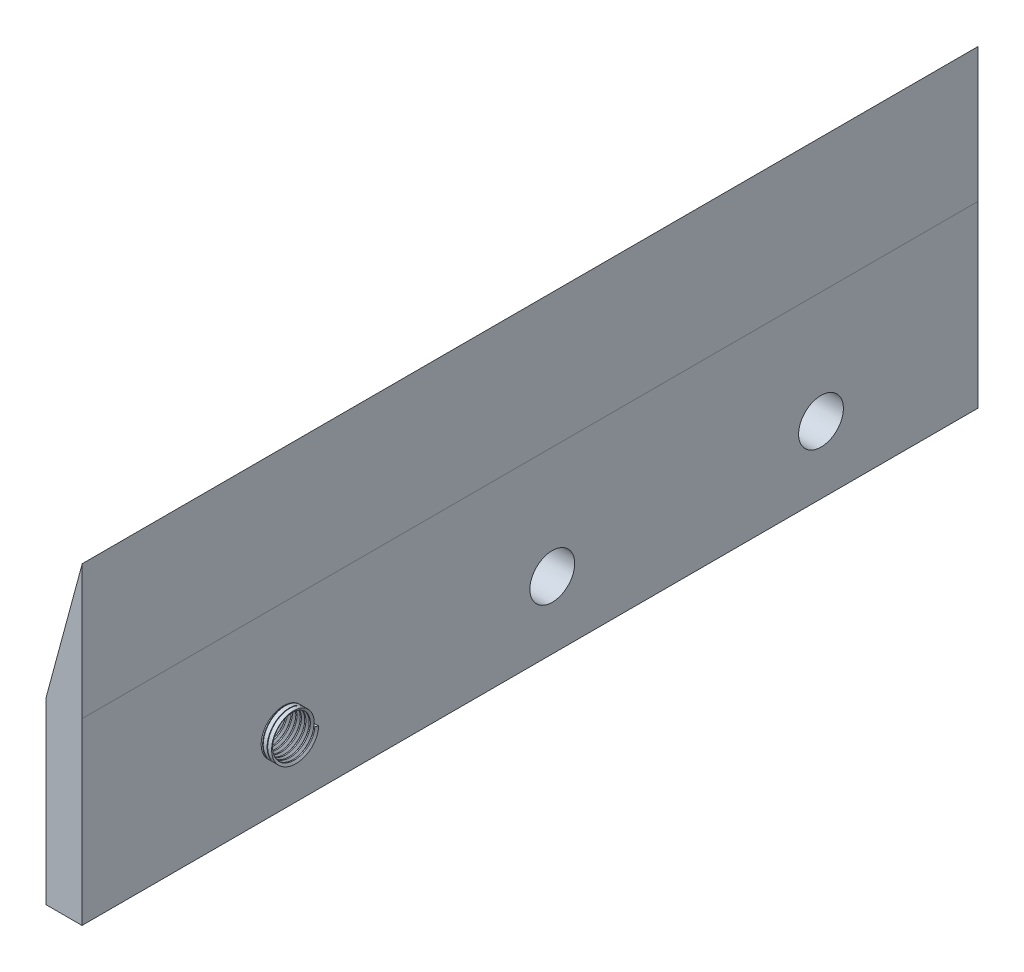
SolidWorks part; units mm, degrees
ref_plane "前基準面" through (0, 0, 0) normal (0, 0, 1) x (1, 0, 0)
ref_plane "上基準面" through (0, 0, 0) normal (0, 1, 0) x (1, 0, 0)
ref_plane "右基準面" through (0, 0, 0) normal (1, 0, 0) x (0, 0, -1)
sketch "草圖1" plane through (0, 0, 0) normal (0, 0, 1) x (1, 0, 0)
  line L0 (206.6624, 1001.1769) -> (198.624, 1001.1769)
  line L1 (198.624, 1001.1769) -> (198.624, 1041.1769)
  line L4 (206.7148, 1071.1628) -> (198.624, 1041.1769) construction
  line L5 (206.7148, 1071.1628) -> (198.624, 1041.1769)
  line L6 (206.7148, 1071.1628) -> (206.6624, 1041.1629) construction
  line L7 (206.7148, 1071.1628) -> (206.6624, 1041.1629)
  line L8 (206.6624, 1041.1629) -> (206.6624, 1001.1769)
  dimension "D1" = 40
  dimension "D2" = 30
  dimension "D3" = 8.0385
extrude "填料-伸長1" add sketch "草圖1" along normal blind 200
ref_plane "平面1" through (198.624, 0, 0) normal (1, 0, 0) x (0, 0, -1)
sketch "草圖2" plane through (198.624, 0, 0) normal (1, 0, 0) x (0, 0, -1)
  line L0 (-200, 1001.1769) -> (0, 1001.1769) construction
  line L1 (0, 1041.1769) -> (0, 1001.1769) construction
  circle A0 centre (-155, 1016.1769) radius 5
  circle A1 centre (-95, 1016.1769) radius 5
  circle A2 centre (-35, 1016.1769) radius 5
  dimension "D1" = 10
  dimension "D2" = 10
  dimension "D3" = 10
  dimension "D4" = 60
  dimension "D5" = 60
  dimension "D6" = 35
  dimension "D7" = 15
extrude "除料-伸長1" cut sketch "草圖2" along normal through all
thread "螺紋1" pitch 1 method extrude profile "螺紋輪廓1" start angle 0, offset 0, length 10, pitch 1, diameter 10
ref_plane "平面2" through (198.624, 1016.1769, 150) normal (0, -1, 0) x (0, 0, -1)
sketch "螺紋輪廓1" plane through (198.624, 1016.1769, 150) normal (0, -1, 0) x (0, 0, -1)
  line L0 (0, 0) -> (0, 1) construction
  line L11 (0, 0) -> (0, 0.875)
  line L12 (0, 0.875) -> (-0.5413, 0.5625)
  line L13 (-0.5413, 0.5625) -> (-0.5413, 0.3125)
  line L15 (-0.5413, 0.3125) -> (0, 0)
  line L17 (-0.5413, 0.4375) -> (0, 0.4375) construction
  point P2 (0, 0)
  dimension "Pitch" = 1
  dimension "Profile_Angle" = 60
  dimension "Profile_Land" = 0.25
  dimension "Profile_Height" = 0.5413
